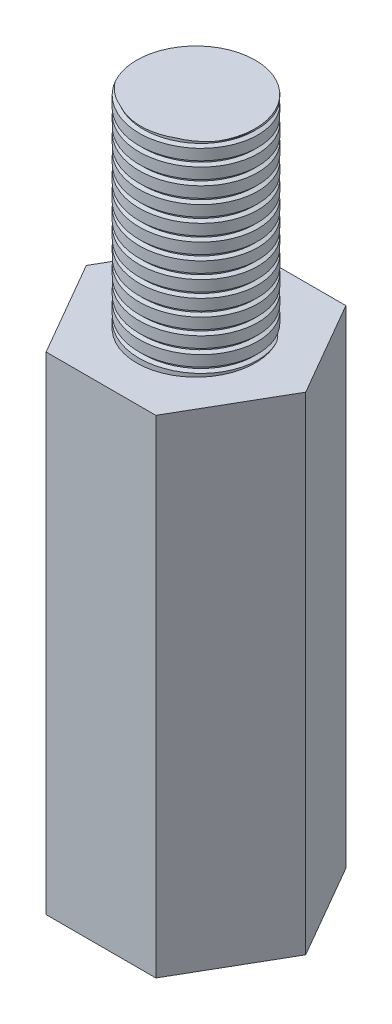
SolidWorks part; units mm, degrees
note: The reader was unsure of these and kept them because the rebuilt part matched: shared geometry of "草图1<3>".
ref_plane "前视基准面" through (0, 0, 0) normal (0, 0, 1) x (1, 0, 0)
ref_plane "上视基准面" through (0, 0, 0) normal (0, 1, 0) x (1, 0, 0)
ref_plane "右视基准面" through (0, 0, 0) normal (1, 0, 0) x (0, 0, -1)
sketch "草图1" plane through (0, 0, 0) normal (0, 1, 0) x (1, 0, 0)
  line L0 (0, 0) -> (0, 4.5761) construction
  line L1 (1.351, -2.34) -> (2.702, 0)
  line L2 (2.702, 0) -> (1.351, 2.34)
  line L3 (1.351, 2.34) -> (-1.351, 2.34)
  line L4 (-1.351, 2.34) -> (-2.702, 0)
  line L5 (-2.702, 0) -> (-1.351, -2.34)
  line L6 (-1.351, -2.34) -> (1.351, -2.34)
  line L7 (0, 4.5761) -> (0, -3.6794) construction
  circle A0 centre (0, 0) radius 2.34 construction
  circle A1 centre (0, 0) radius 1.46
  dimension "D1" = 4.68
  dimension "D2" = 2.92
extrude "凸台-拉伸1" add sketch "草图1" along normal blind 12 contours A1 | L5 L6 L1 L2 L3 L4 A1
extrude "切除-拉伸1" cut sketch "草图1<3>" along normal blind 5 contours A1
sketch "草图1<3>" plane through (0, 0, 0) normal (0, 1, 0) x (1, 0, 0) same geometry as "草图1"
sketch "草图2" plane through (0, 12, 0) normal (0, 1, 0) x (1, 0, 0)
  circle A0 centre (0, 0) radius 1.46
  dimension "D1" = 2.92
extrude "凸台-拉伸2" add sketch "草图2" along normal blind 5 separate body
ref_plane "基准面1" through (0, 0, 0) normal (0, 0, -1) x (-1, 0, 0)
sketch "草图4" plane through (0, 0, 0) normal (0, 0, -1) x (-1, 0, 0)
  line L0 (0, 0) -> (0, 28.5702) construction
  line L1 (-1.56, 12) -> (-1.56, 12.2)
  line L2 (-1.56, 12.2) -> (-1.36, 12.1333)
  line L3 (-1.36, 12.0667) -> (-1.56, 12)
  line L4 (-1.26, 12.1) -> (-2.0659, 12.1) construction
  line L5 (-2.0659, 12.1) -> (-0.8933, 12.1) construction
  line L7 (-1.46, 17) -> (-1.46, 12) construction
  line L8 (-1.36, 12.1333) -> (-1.36, 12.0667)
  line L9 (-1.46, 12) -> (1.46, 12) construction
  point P14 (0, 0)
  point P15 (0, 0)
  dimension "D1" = 0.1
  dimension "D2" = 0.1
  dimension "D3" = 0.1
  dimension "D4" = 0.3
  dimension "D5" = 0.2
  dimension "D6" = 0.1
  dimension "D7" = 0.0667
  dimension "D8" = 0.0667
ref_plane "基准面2" through (0, 12.1, 0) normal (0, 1, 0) x (1, 0, 0)
sketch "草图5" plane through (0, 12.1, 0) normal (0, 1, 0) x (1, 0, 0)
  circle A0 centre (0, 0) radius 1.46
  dimension "D1" = 2.92
curve "螺旋线/涡状线1" pitch 0.4 height 7.5 turns 18.75
sweep "切除-扫描1" cut profiles "草图4" path "螺旋线/涡状线1"
sketch "草图6" plane through (0, 0, 0) normal (0, -1, 0) x (1, 0, 0)
  circle A0 centre (0, 0) radius 1.46
curve "螺旋线/涡状线2" pitch 0.4 height 9.5 turns 23.75
sketch "草图7" plane through (0, 0, 0) normal (0, 0, -1) x (-1, 0, 0)
  line L0 (1.46, 0.2) -> (1.66, 0.1333)
  line L1 (1.66, 0.0667) -> (1.46, 0)
  line L2 (1.46, 0.2) -> (1.46, 0)
  line L3 (1.66, 0.1333) -> (1.66, 0.0667)
  line L8 (1.351, 0) -> (-1.351, 0) construction
  dimension "D1" = 0.2
  dimension "D3" = 1.46
  dimension "D4" = 0.2
sweep "切除-扫描2" cut profiles "草图7" path "螺旋线/涡状线2"
equation "\"chang\"= 20mm"
equation "\"r\"= 2.92mm"
equation "\"luowengao\"= 6.5mm"
equation "\"rr\"= 4.68mm"
equation "\"D1@草图1\"=\"rr\""
equation "\"D2@草图1\"=\"r\""
equation "\"D1@凸台-拉伸1\"=\"chang\""
equation "\"D1@切除-拉伸1\"=\"luowengao\"+5mm"
equation "\"D1@草图2\"=\"r\""
equation "\"D1@凸台-拉伸2\"=\"luowengao\""
